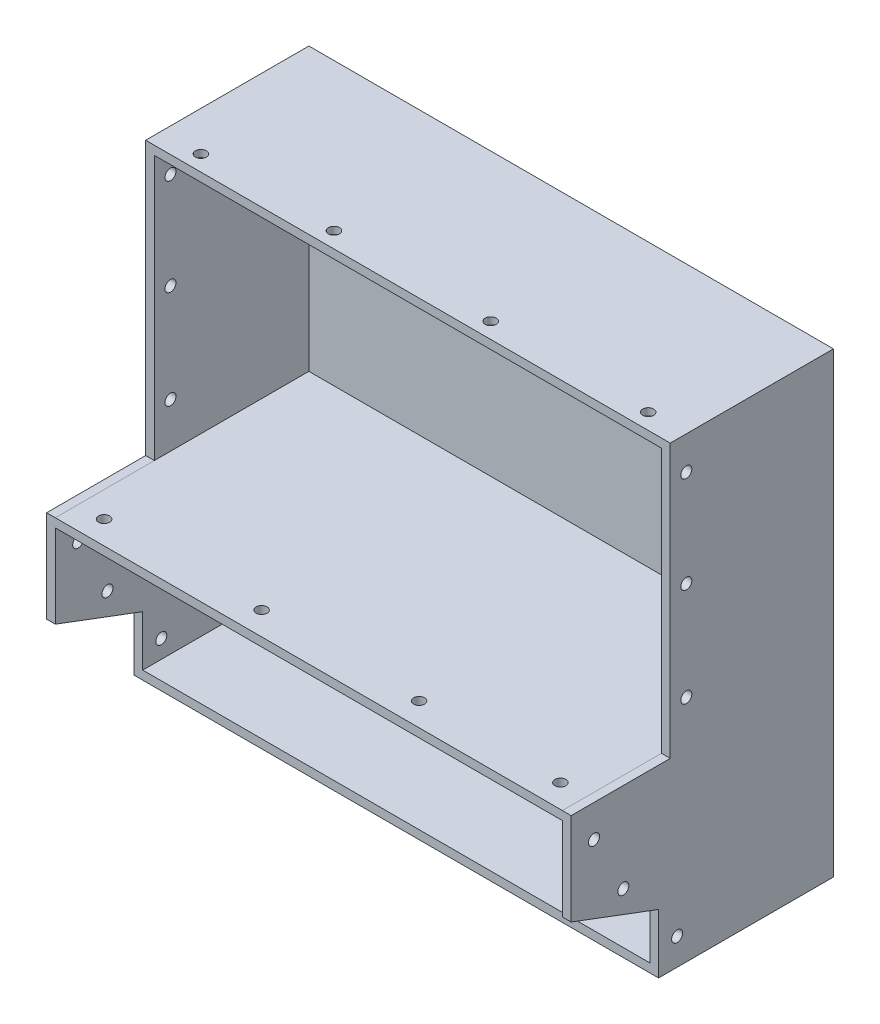
SolidWorks part; units mm, degrees
material "Custom Plastic"
ref_plane "X-Y Datum" through (0, 0, 0) normal (0, 0, 1) x (1, 0, 0)
ref_plane "X-Z Datum" through (0, 0, 0) normal (0, 1, 0) x (1, 0, 0)
ref_plane "Y-Z Datum" through (0, 0, 0) normal (1, 0, 0) x (0, 0, -1)
sketch "Sketch1" plane through (0, 0, 0) normal (0, 0, 1) x (1, 0, 0)
  line L1 (-95.25, -83.058) -> (95.25, -83.058)
  line L2 (-95.25, -83.058) -> (-95.25, 83.058)
  line L3 (-95.25, 83.058) -> (95.25, 83.058)
  line L4 (95.25, -83.058) -> (95.25, 83.058)
  line L5 (-95.25, -83.058) -> (95.25, 83.058) construction
  line L6 (-95.25, 83.058) -> (95.25, -83.058) construction
  point P0 (0, 0)
  dimension "D1" = 166.116
  dimension "D2" = 190.5
extrude "Boss-Extrude1" add sketch "Sketch1" along normal blind 95.25
sketch "Sketch3" plane through (0, 0, 95.25) normal (0, 0, 1) x (1, 0, 0)
  line L0 (-92.075, -49.9618) -> (92.075, -49.9618)
  line L1 (92.075, -61.8913) -> (95.25, -61.8913)
  line L2 (-92.075, -61.8913) -> (92.075, -61.8913)
  line L3 (95.25, -83.058) -> (95.25, 83.058) construction
  line L4 (-92.075, -61.8913) -> (-92.075, -79.883)
  line L5 (-95.25, -49.9618) -> (-95.25, -61.8913)
  line L6 (92.075, -61.8913) -> (92.075, -79.883)
  line L7 (-95.25, 83.058) -> (-95.25, -83.058) construction
  line L8 (-122.0928, 3.2687) -> (-122.1486, 3.2687)
  line L9 (92.075, -79.883) -> (76.2531, -79.883)
  line L13 (-95.25, 32.8917) -> (-92.075, 32.8917)
  line L15 (-122.0786, -16.0951) -> (-122.1486, -16.0951)
  line L17 (95.25, -49.9618) -> (92.075, -49.9618)
  line L18 (-92.075, -79.883) -> (76.2531, -79.883)
  line L21 (-92.075, -49.9618) -> (-95.25, -49.9618)
  line L23 (-81.0858, 79.883) -> (83.8833, 79.883)
  line L25 (-81.0858, 79.883) -> (-92.075, 79.883)
  line L26 (-92.075, 79.883) -> (-92.075, -16.0951)
  line L28 (95.25, 48.6627) -> (92.075, 48.6627)
  line L30 (83.8833, 79.883) -> (92.075, 79.883)
  line L31 (92.075, 79.883) -> (92.075, -16.0951)
  line L33 (-92.075, -16.0951) -> (92.075, -16.0951)
  line L34 (95.25, -49.9618) -> (95.25, -61.8913)
  line L35 (-95.25, -61.8913) -> (-92.075, -61.8913)
extrude "Cut-Extrude1" cut sketch "Sketch3" against normal blind 92.075 contours L23 region at (0, 31.8939, 95.25)
sketch "Sketch15" plane through (0, 0, 95.25) normal (0, 0, 1) x (1, 0, 0)
  line L1 (-95.25, 83.058) -> (-95.25, -83.058) construction
  line L3 (95.25, -83.058) -> (95.25, 83.058) construction
  line L4 (95.25, -16.1093) -> (95.25, 83.058)
  line L5 (95.25, 83.058) -> (-95.25, 83.058)
  line L6 (-95.25, 83.058) -> (-95.25, -16.1093)
  line L10 (95.25, -16.1093) -> (92.075, -16.0951)
  line L11 (92.075, -16.0951) -> (92.075, 79.883)
  line L12 (92.075, 79.883) -> (-92.075, 79.883)
  line L13 (-92.075, 79.883) -> (-92.075, -16.0951)
  line L14 (-92.075, -16.0951) -> (92.075, -16.0951) construction
  line L15 (-92.075, 79.883) -> (-92.075, -16.0951) construction
  line L16 (-95.25, -16.1093) -> (-92.075, -16.0951)
extrude "Cut-Extrude5" cut sketch "Sketch15" against normal blind 35.9842
sketch "Sketch17" plane through (0, 0, 95.25) normal (0, 0, 1) x (1, 0, 0)
  line L0 (-95.25, -49.5836) -> (-95.25, -83.058)
  line L2 (-95.25, -83.058) -> (95.25, -83.058)
  line L3 (-95.25, -16.1093) -> (-95.25, -83.058) construction
  line L4 (95.25, -83.058) -> (95.25, -16.1093) construction
  line L5 (95.25, -83.058) -> (95.25, -49.5836)
  line L6 (-95.25, -49.5836) -> (95.25, -49.5836)
extrude "Cut-Extrude6" cut sketch "Sketch17" against normal blind 31.75
sketch "Sketch18" plane through (-95.25, 0, 0) normal (-1, 0, 0) x (0, 0, 1)
  line L0 (63.5, -49.5836) -> (63.5, -61.5061)
  line L1 (63.5, -49.5836) -> (63.5, -83.058) construction
  line L2 (63.5, -61.5061) -> (95.25, -49.5836)
  line L3 (95.25, -49.5836) -> (63.5, -49.5836)
extrude "Boss-Extrude8" add sketch "Sketch18" against normal blind 190.5
sketch "Sketch19" plane through (0, 0, 95.25) normal (0, 0, 1) x (1, 0, 0)
  line L0 (-92.075, -19.2701) -> (-92.075, -49.5836)
  line L2 (95.25, -49.5836) -> (-95.25, -49.5836) construction
  line L4 (92.075, -19.2701) -> (92.075, -49.5836)
  line L6 (92.075, -49.5836) -> (-92.075, -49.5836)
  line L8 (-92.075, -19.2701) -> (92.075, -19.2701)
extrude "Cut-Extrude7" cut sketch "Sketch19" against normal blind 92.075
sketch "Sketch20" plane through (0, -74.8032, 28.0894) normal (0, -0.9362, 0.3515) x (1, 0, 0)
  line L2 (-92.075, -3.8019) -> (-92.075, 82.3961) construction
  line L4 (-92.075, 71.7396) -> (92.075, 71.7396) construction
  line L6 (-92.075, 71.7396) -> (92.075, 71.7396)
  line L12 (92.075, -3.8019) -> (92.075, 82.3961) construction
  line L13 (95.25, 71.7396) -> (92.075, 71.7396) construction
  line L15 (-92.075, 71.7396) -> (-92.075, 37.8249)
  line L16 (95.25, 37.8249) -> (-95.25, 37.8249) construction
  line L17 (92.075, 71.7396) -> (92.075, 37.8249)
  line L18 (92.075, 37.8249) -> (-92.075, 37.8249)
extrude "Cut-Extrude8" cut sketch "Sketch20" against normal blind 13.175
sketch "Sketch21" plane through (0, 0, 63.5) normal (0, 0, 1) x (1, 0, 0)
  line L0 (-92.075, -61.5061) -> (-92.075, -49.5836)
  line L2 (-92.075, -49.5836) -> (92.075, -49.5836)
  line L4 (92.075, -49.5836) -> (92.075, -61.5061)
  line L6 (-92.075, -61.5061) -> (-92.075, -79.883)
  line L7 (-92.075, -79.883) -> (92.075, -79.883)
  line L8 (92.075, -79.883) -> (92.075, -61.5061)
extrude "Cut-Extrude9" cut sketch "Sketch21" against normal blind 60.325
sketch "Sketch23" plane through (0, -83.058, 0) normal (0, -1, 0) x (1, 0, 0)
  circle A4 centre (-82.8492, 55.0007) radius 2
  circle A5 centre (-25.472, 55.0007) radius 2
  circle A6 centre (31.5236, 55.0007) radius 2
  circle A7 centre (82.8147, 55.0007) radius 2
extrude "Cut-Extrude10" cut sketch "Sketch23" against normal blind 2.54
sketch "Sketch24" plane through (0, 83.058, 0) normal (0, 1, 0) x (1, 0, 0)
  line L0 (81.5233, -53.5508) -> (-86.3243, -53.5508) construction
  line L1 (95.25, -59.2658) -> (-95.25, -59.2658) construction
  circle A0 centre (81.5233, -53.5508) radius 2
  circle A3 centre (24.3357, -53.5508) radius 2
  circle A4 centre (-32.5907, -53.5508) radius 2
  circle A7 centre (-80.8952, -53.5508) radius 2
  dimension "D1" = 5.715
extrude "Cut-Extrude11" cut sketch "Sketch24" against normal blind 2.54
sketch "Sketch25" plane through (95.25, 0, 0) normal (1, 0, 0) x (0, 0, -1)
  circle A0 centre (-53.4238, 70.993) radius 2
  circle A1 centre (-53.4238, 35.941) radius 2
  circle A4 centre (-53.4238, 0.889) radius 2 [skipped]
  circle A6 centre (-53.4238, 0.2178) radius 2
  dimension "D2" = 3
extrude "Cut-Extrude12" cut sketch "Sketch25" against normal through all
sketch "Sketch26" plane through (0, -16.0951, 0) normal (0, 1, 0) x (1, 0, 0)
  line L1 (92.075, -59.2658) -> (92.075, -95.25) construction
  line L2 (92.075, -63.7108) -> (-92.075, -63.7108)
  line L3 (-92.075, -59.2658) -> (-92.075, -95.25) construction
  line L5 (-92.075, -78.6639) -> (92.075, -78.6639)
sketch "Sketch27" plane through (0, -16.0951, 0) normal (0, 1, 0) x (1, 0, 0)
  circle A0 centre (82.9278, -86.8228) radius 2
  circle A8 centre (31.5919, -86.8228) radius 2
  circle A11 centre (-25.6023, -86.8228) radius 2
  circle A12 centre (-82.8005, -86.8228) radius 2
extrude "Cut-Extrude13" cut sketch "Sketch27" against normal blind 3.175
sketch "Sketch28" plane through (95.25, 0, 0) normal (1, 0, 0) x (0, 0, -1)
  circle A0 centre (-56.7612, -73.2851) radius 2
  circle A1 centre (-76.307, -48.5678) radius 2
  circle A2 centre (-86.9498, -27.7945) radius 2
extrude "Cut-Extrude15" cut sketch "Sketch28" against normal through all
sketch "Sketch29" plane through (95.25, 0, 0) normal (1, 0, 0) x (0, 0, -1)
  line L0 (-78.6639, -16.1093) -> (-78.6639, -37.7454)
  line L1 (-59.2658, -16.1093) -> (-95.25, -16.1093) construction
  line L2 (-79.8732, -37.7454) -> (-78.6639, -37.7454)
  line L4 (-76.564, -56.6004) -> (-70.7333, -41.0729)
  line L5 (-63.5, -61.5061) -> (-95.25, -49.5836) construction
  line L6 (-70.7333, -41.0729) -> (-87.4612, -34.9829)
  line L8 (-46.9139, -83.058) -> (-46.9139, -60.9915)
  line L9 (-63.5, -83.058) -> (0, -83.058) construction
  line L10 (-70.7333, -41.0729) -> (-50.1989, -48.6541)
